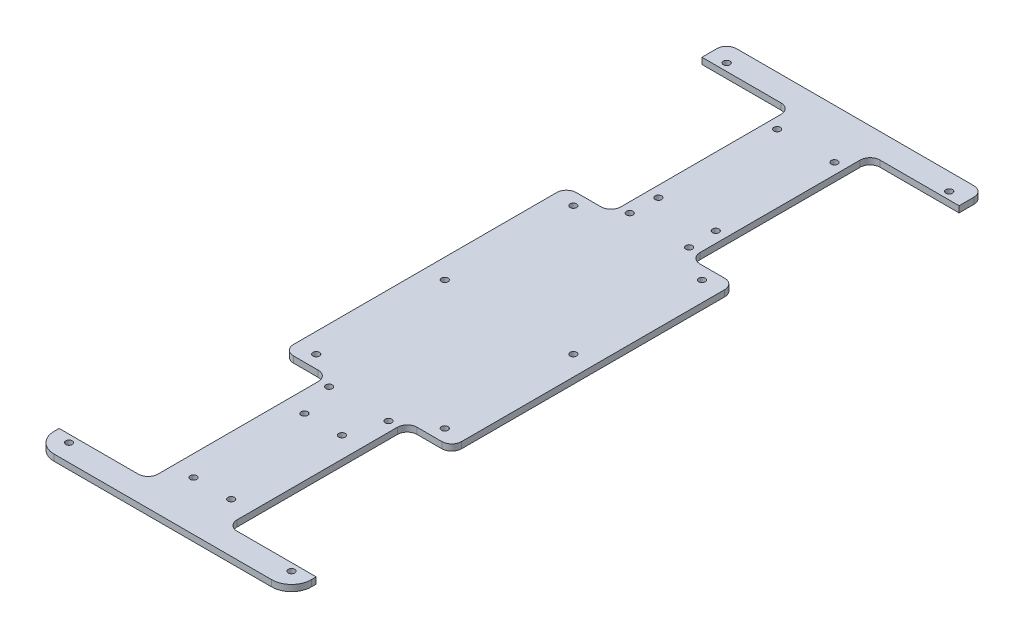
SolidWorks part; units mm, degrees
ref_plane "Front Plane" through (0, 0, 0) normal (0, 0, 1) x (1, 0, 0)
ref_plane "Top Plane" through (0, 0, 0) normal (0, 1, 0) x (1, 0, 0)
ref_plane "Right Plane" through (0, 0, 0) normal (1, 0, 0) x (0, 0, -1)
sketch "Sketch1" plane through (0, 0, 0) normal (0, 1, 0) x (1, 0, 0)
  line L0 (0, 0) -> (130, 0)
  line L1 (0, 0) -> (130, 0) construction
  line L2 (0, 0) -> (0, 350) construction
  line L3 (0, 350) -> (130, 350) construction
  line L4 (130, 0) -> (130, 350) construction
  line L5 (130, 0) -> (130, 12.5)
  line L6 (130, 12.5) -> (85, 12.5)
  line L7 (85, 12.5) -> (85, 103.5)
  line L11 (85, 246.5) -> (85, 337.5)
  line L12 (85, 337.5) -> (130, 337.5)
  line L13 (130, 337.5) -> (130, 350)
  line L14 (130, 350) -> (0, 350)
  line L15 (0, 350) -> (0, 337.5)
  line L16 (0, 337.5) -> (45, 337.5)
  line L17 (45, 337.5) -> (45, 246.5)
  line L21 (45, 103.5) -> (45, 12.5)
  line L22 (45, 12.5) -> (0, 12.5)
  line L23 (0, 12.5) -> (0, 0)
  line L24 (45, 246.5) -> (22.5, 246.5)
  line L25 (22.5, 246.5) -> (22.5, 103.5)
  line L26 (22.5, 103.5) -> (45, 103.5)
  line L27 (85, 246.5) -> (107.5, 246.5)
  line L28 (107.5, 246.5) -> (107.5, 103.5)
  line L29 (107.5, 103.5) -> (85, 103.5)
  dimension "D1" = 130
  dimension "D2" = 350
  dimension "D3" = 45
  dimension "D4" = 91
  dimension "D5" = 22.5
  dimension "D6" = 143
extrude "Boss-Extrude1" add sketch "Sketch1" along normal blind 3.175
fillet "Fillet1" radius 10 2 edges at (130, 1.5875, 0) (0, 1.5875, 0)
fillet "Fillet2" radius 5 6 edges at (0, 1.5875, -350) (130, 1.5875, -350) (107.5, 1.5875, -246.5) (107.5, 1.5875, -103.5) (22.5, 1.5875, -103.5) (22.5, 1.5875, -246.5)
sketch "Sketch2" plane through (0, 3.175, 0) normal (0, 1, 0) x (1, 0, 0)
  line L2 (32.5, 240) -> (32.5, 110) construction
  line L3 (22.5, 175) -> (32.5, 175) construction
  line L4 (22.5, 241.5) -> (22.5, 108.5) construction
  line L5 (65, 350) -> (65, 0) construction
  line L6 (125, 350) -> (5, 350) construction
  line L7 (10, 0) -> (120, 0) construction
  circle A0 centre (32.5, 240) radius 1.65
  circle A1 centre (32.5, 175) radius 1.65
  circle A2 centre (32.5, 110) radius 1.65
  circle A3 centre (97.5, 110) radius 1.65
  circle A4 centre (97.5, 175) radius 1.65
  circle A5 centre (97.5, 240) radius 1.65
  dimension "D3" = 3.3
  dimension "D1" = 10
  dimension "D2" = 130
extrude "Cut-Extrude1" cut sketch "Sketch2" against normal through all
sketch "Sketch3" plane through (0, 3.175, 0) normal (0, 1, 0) x (1, 0, 0)
  line L0 (0, 12.5) -> (8.75, 12.5) construction
  line L1 (45, 12.5) -> (0, 12.5) construction
  line L2 (8.75, 12.5) -> (8.75, 8.75) construction
  line L3 (65, 0) -> (65, 57.6288) construction
  line L4 (10, 0) -> (120, 0) construction
  circle A0 centre (8.75, 8.75) radius 1.65
  circle A1 centre (121.25, 8.75) radius 1.65
  dimension "D3" = 3.3
  dimension "D1" = 8.75
  dimension "D2" = 3.75
extrude "Cut-Extrude2" cut sketch "Sketch3" against normal through all
sketch "Sketch4" plane through (0, 3.175, 0) normal (0, 1, 0) x (1, 0, 0)
  line L0 (0, 337.5) -> (8.75, 337.5) construction
  line L1 (0, 337.5) -> (45, 337.5) construction
  line L2 (8.75, 337.5) -> (8.75, 341.25) construction
  line L3 (65, 350) -> (65, 288.2737) construction
  line L4 (125, 350) -> (5, 350) construction
  circle A0 centre (8.75, 341.25) radius 1.65
  circle A1 centre (121.25, 341.25) radius 1.65
  dimension "D3" = 3.3
  dimension "D1" = 8.75
  dimension "D2" = 3.75
extrude "Cut-Extrude3" cut sketch "Sketch4" against normal through all
fillet "Fillet3" radius 5 8 edges at (85, 1.5875, -246.5) (45, 1.5875, -246.5) (85, 1.5875, -103.5) (45, 1.5875, -103.5) (45, 1.5875, -12.5) (85, 1.5875, -12.5) (45, 1.5875, -337.5) (85, 1.5875, -337.5)
sketch "Sketch5" plane through (0, 3.175, 0) normal (0, 1, 0) x (1, 0, 0)
  line L0 (65, 0) -> (65, 350) construction
  line L1 (55.5, 81) -> (74.5, 81) construction
  line L2 (55.5, 81) -> (55.5, 25) construction
  line L3 (55.5, 25) -> (74.5, 25) construction
  line L4 (74.5, 81) -> (74.5, 25) construction
  line L5 (10, 0) -> (120, 0) construction
  line L6 (125, 350) -> (5, 350) construction
  line L8 (50.5, 325) -> (79.5, 325) construction
  line L9 (50.5, 325) -> (50.5, 265) construction
  line L10 (50.5, 265) -> (79.5, 265) construction
  line L11 (79.5, 325) -> (79.5, 265) construction
  circle A0 centre (55.5, 81) radius 1.65
  circle A1 centre (74.5, 81) radius 1.65
  circle A2 centre (74.5, 25) radius 1.65
  circle A3 centre (55.5, 25) radius 1.65
  circle A4 centre (79.5, 325) radius 1.65
  circle A5 centre (50.5, 325) radius 1.65
  circle A6 centre (79.5, 265) radius 1.65
  circle A7 centre (50.5, 265) radius 1.65
  point P10 (65, 25)
  point P19 (65, 325)
  dimension "D4" = 3.3
  dimension "D8" = 3.3
  dimension "D1" = 19
  dimension "D2" = 56
  dimension "D3" = 25
  dimension "D5" = 29
  dimension "D6" = 60
  dimension "D7" = 25
extrude "Cut-Extrude4" cut sketch "Sketch5" against normal blind 10
sketch "Sketch6" plane through (0, 3.175, 0) normal (0, 1, 0) x (1, 0, 0)
  line L0 (65, 350) -> (65, 0) construction
  line L1 (50, 251) -> (80, 251) construction
  line L2 (50, 251) -> (50, 99) construction
  line L3 (50, 99) -> (80, 99) construction
  line L4 (80, 251) -> (80, 99) construction
  line L5 (125, 350) -> (5, 350) construction
  line L6 (10, 0) -> (120, 0) construction
  line L7 (22.5, 175) -> (107.5, 175) construction
  line L8 (22.5, 241.5) -> (22.5, 108.5) construction
  line L9 (107.5, 108.5) -> (107.5, 241.5) construction
  circle A0 centre (80, 99) radius 1.65
  circle A1 centre (50, 99) radius 1.65
  circle A2 centre (80, 251) radius 1.65
  circle A3 centre (50, 251) radius 1.65
  point P8 (65, 99)
  point P21 (80, 175)
  dimension "D3" = 3.3
  dimension "D1" = 152
  dimension "D2" = 30
extrude "Cut-Extrude5" cut sketch "Sketch6" against normal through all
